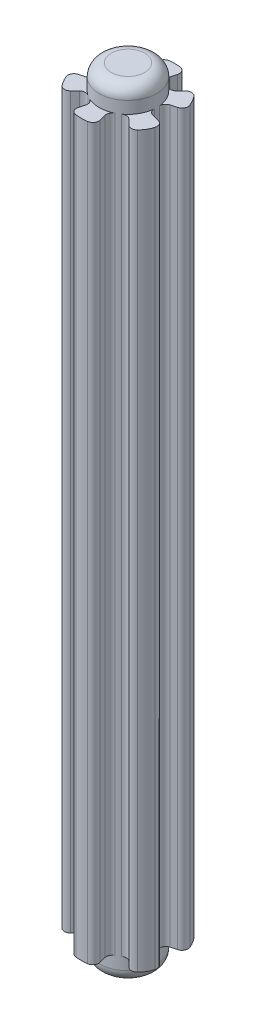
SolidWorks part; units mm, degrees
ref_plane "Front Plane" through (0, 0, 0) normal (0, 0, 1) x (1, 0, 0)
ref_plane "Top Plane" through (0, 0, 0) normal (0, 1, 0) x (1, 0, 0)
ref_plane "Right Plane" through (0, 0, 0) normal (1, 0, 0) x (0, 0, -1)
sketch "Sketch2" plane through (0, 0, 0) normal (0, 1, 0) x (1, 0, 0)
  line L0 (0, 0) -> (0.0739, 0)
  line L2 (2.3008, -0.5891) -> (3.7752, -0.9786)
  line L3 (0.0739, 0) -> (0.1042, -0.0303)
  line L4 (0, 0) -> (0.0858, -0.0446)
  line L5 (1.6802, 1.6786) -> (2.7413, 2.7388)
  line L6 (-1.6794, 1.6794) -> (-2.74, 2.74)
  line L8 (0.6147, 2.2941) -> (1.0029, 3.743)
  line L9 (-0.6147, 2.2941) -> (-1.0029, 3.743)
  line L10 (2.2941, 0.6147) -> (3.743, 1.0029)
  line L11 (0, 0) -> (0.1042, -0.0303)
  line L12 (-2.2941, 0.6147) -> (-3.743, 1.0029)
  line L13 (0.0739, 0) -> (0.0858, -0.0446)
  line L14 (-0.6147, -2.2941) -> (-1.0029, -3.743)
  line L15 (-2.2941, -0.6147) -> (-3.743, -1.0029)
  line L16 (-1.6794, -1.6794) -> (-2.74, -2.74)
  line L17 (0.6814, -2.2752) -> (1.0684, -3.7248)
  line L18 (1.7145, -1.6435) -> (2.7672, -2.6981)
  arc A0 (-2.2941, 0.6147) -> (-2.2941, -0.6147) centre (0, 0) ccw
  arc A1 (-2.74, 2.74) -> (-3.743, 1.0029) centre (0, 0) ccw
  arc A2 (1.0029, 3.743) -> (-1.0029, 3.743) centre (0, 0) ccw
  arc A3 (3.743, 1.0029) -> (2.7413, 2.7388) centre (0, 0) ccw
  arc A5 (-1.0029, -3.743) -> (1.0684, -3.7248) centre (0, 0) ccw
  arc A6 (-3.743, -1.0029) -> (-2.74, -2.74) centre (0, 0) ccw
  arc A7 (-2.74, 2.74) -> (-3.743, 1.0029) centre (0, 0) ccw
  arc A8 (1.0029, 3.743) -> (-1.0029, 3.743) centre (0, 0) ccw
  arc A9 (3.743, 1.0029) -> (2.7413, 2.7388) centre (0, 0) ccw
  arc A10 (-3.743, -1.0029) -> (-2.74, -2.74) centre (0, 0) ccw
  arc A11 (-1.0029, -3.743) -> (1.0684, -3.7248) centre (0, 0) ccw
  arc A12 (2.7672, -2.6981) -> (3.7752, -0.9786) centre (1.7753, -0.9614) ccw
  arc A13 (-0.6147, 2.2941) -> (-1.6794, 1.6794) centre (0, 0) ccw
  arc A14 (1.6802, 1.6786) -> (0.6147, 2.2941) centre (0, 0) ccw
  arc A15 (2.3008, -0.5891) -> (2.2941, 0.6147) centre (0, 0) ccw
  arc A16 (0.6814, -2.2752) -> (1.7145, -1.6435) centre (0, 0) ccw
  arc A17 (-1.6794, -1.6794) -> (-0.6147, -2.2941) centre (0, 0) ccw
  dimension "D1" = 3.875
  dimension "D2" = 2.375
extrude "Boss-Extrude1" add sketch "Sketch2" along normal blind 60 contours L16 A17 L14 A5 L17 A16 L18 A12 L2 A15 L10 A3 L5 A14 L8 A2 L9 A13 L6 A1 L12 A0 L15 A6 L11 L13 L4 L0 L3 region at (0.0225, 0, 0.0171)
sketch "Sketch4" plane through (0, 60, 0) normal (0, 1, 0) x (1, 0, 0)
  circle A0 centre (0, 0) radius 2.375
  dimension "D1" = 4.75
extrude "Boss-Extrude3" add sketch "Sketch4" along normal blind 2
fillet "Fillet1" radius 0.5 24 edges at (-2.74, 30, -2.74) (-1.6794, 30, -1.6794) (-0.6147, 30, -2.2941) (-1.0029, 30, -3.743) (1.0029, 30, -3.743) (0.6147, 30, -2.2941) (1.6802, 30, -1.6786) (2.7413, 30, -2.7388) (3.743, 30, -1.0029) (2.2941, 30, -0.6147) (2.3008, 30, 0.5891) (3.7752, 30, 0.9786) (2.7672, 30, 2.6981) (1.7145, 30, 1.6435) (0.6814, 30, 2.2752) (-1.6794, 30, 1.6794) (-2.2941, 30, 0.6147) (-2.2941, 30, -0.6147) (-0.6147, 30, 2.2941) (-3.743, 30, -1.0029) (-3.743, 30, 1.0029) (-2.74, 30, 2.74) (-1.0029, 30, 3.743) (1.0684, 30, 3.7248)
sketch "Sketch6" plane through (0, 0, 0) normal (0, -1, 0) x (1, 0, 0)
  circle A0 centre (0, 0) radius 2.375
  dimension "D1" = 4.75
extrude "Boss-Extrude5" add sketch "Sketch6" along normal blind 2
fillet "Fillet2" radius 1 2 edges at (0, 62, 2.375) (0, -2, -2.375)
